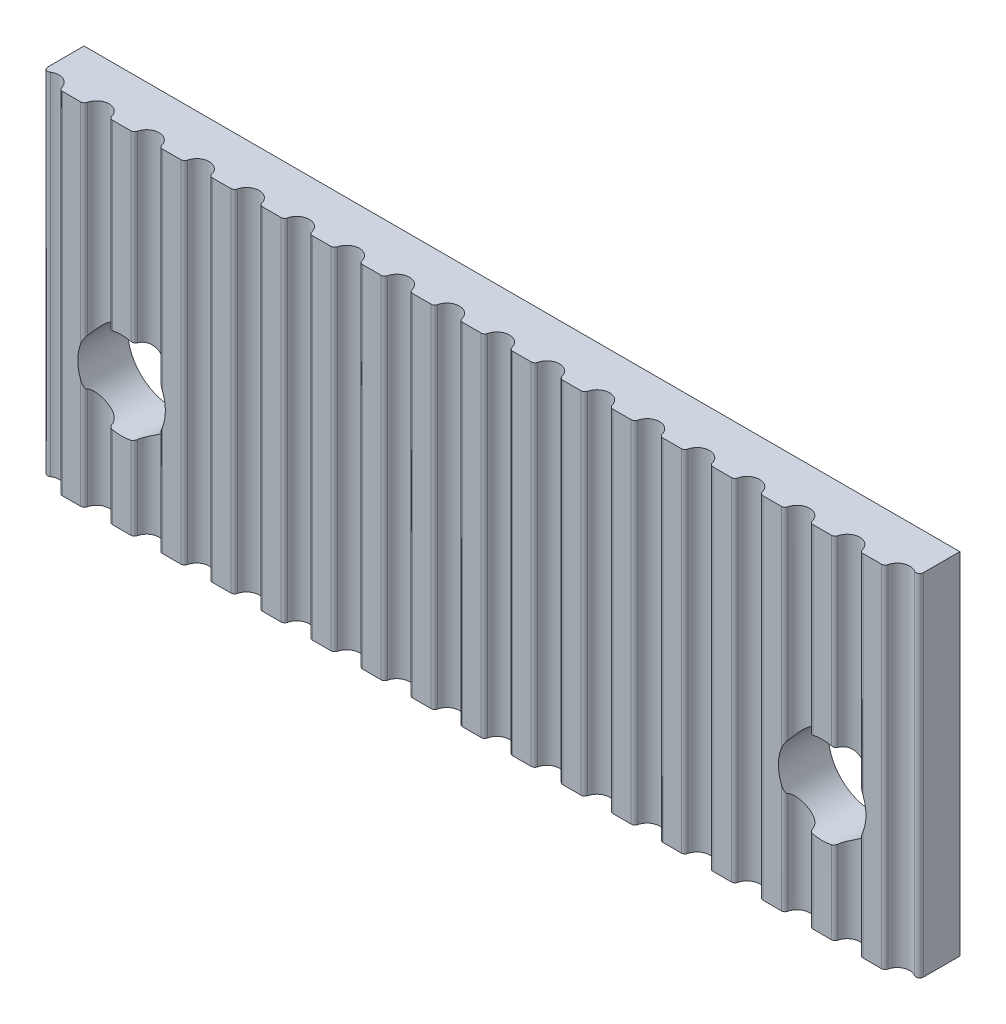
SolidWorks part; units mm, degrees
material "ABS"
ref_plane "Front Plane" through (0, 0, 0) normal (0, 0, 1) x (1, 0, 0)
ref_plane "Top Plane" through (0, 0, 0) normal (0, 1, 0) x (1, 0, 0)
ref_plane "Right Plane" through (0, 0, 0) normal (1, 0, 0) x (0, 0, -1)
sketch "Sketch1" plane through (0, 0, 0) normal (0, 1, 0) x (1, 0, 0)
  line L1 (-17.5, -1) -> (17.5, -1)
  line L2 (-17.5, -1) -> (-17.5, 1)
  line L3 (-17.5, 1) -> (17.5, 1)
  line L4 (17.5, -1) -> (17.5, 1)
  line L5 (-17.5, -1) -> (17.5, 1) construction
  line L6 (-17.5, 1) -> (17.5, -1) construction
  point P0 (0, 0)
  dimension "D1" = 2
  dimension "D2" = 35
extrude "Boss-Extrude1" add sketch "Sketch1" along normal blind 14
sketch "Sketch2" plane through (0, 0, 1) normal (0, 0, 1) x (1, 0, 0)
  line L0 (-17.5, 14) -> (-17.5, 0) construction
  line L1 (-17.5, 0) -> (17.5, 0) construction
  line L2 (17.5, 14) -> (17.5, 0) construction
  circle A0 centre (-14, 5) radius 1.75
  circle A1 centre (14, 5) radius 1.75
  dimension "D1" = 3.5
  dimension "D3" = 5
  dimension "D4" = 3.5
  dimension "D2" = 3.5
  dimension "D5" = 3.5
extrude "Cut-Extrude1" cut sketch "Sketch2" against normal blind 14
sketch "Sketch3" plane through (0, 14, 0) normal (0, 1, 0) x (1, 0, 0)
  line L0 (-17.5, -1) -> (17.5, -1) construction
  circle A0 centre (-17, -1) radius 0.5
  dimension "D1" = 1
extrude "Cut-Extrude2" cut sketch "Sketch3" against normal through all
pattern_linear "LPattern1" count 18 spacing 2 along (1, 0, 0) of "Cut-Extrude2"
fillet "Fillet1" radius 0.15 44 edges at (-16.5, 7, 1) (-17.5, 7, 1) (-15.5, 9.9507, 1) (12.5, 2.0493, 1) (13.5, 1.6615, 1) (14.5, 1.6615, 1) (15.5, 2.0493, 1) (17.5, 7, 1) (16.5, 7, 1) (15.5, 9.9507, 1) (14.5, 10.3385, 1) (13.5, 10.3385, 1) (12.5, 9.9507, 1) (11.5, 7, 1) (10.5, 7, 1) (9.5, 7, 1) (8.5, 7, 1) (7.5, 7, 1) (6.5, 7, 1) (5.5, 7, 1) (4.5, 7, 1) (3.5, 7, 1) (2.5, 7, 1) (1.5, 7, 1) (0.5, 7, 1) (-0.5, 7, 1) (-1.5, 7, 1) (-2.5, 7, 1) (-3.5, 7, 1) (-4.5, 7, 1) (-5.5, 7, 1) (-6.5, 7, 1) (-7.5, 7, 1) (-8.5, 7, 1) (-12.5, 9.9507, 1) (-13.5, 10.3385, 1) (-14.5, 10.3385, 1) (-9.5, 7, 1) (-10.5, 7, 1) (-11.5, 7, 1) (-12.5, 2.0493, 1) (-13.5, 1.6615, 1) (-14.5, 1.6615, 1) (-15.5, 2.0493, 1)
